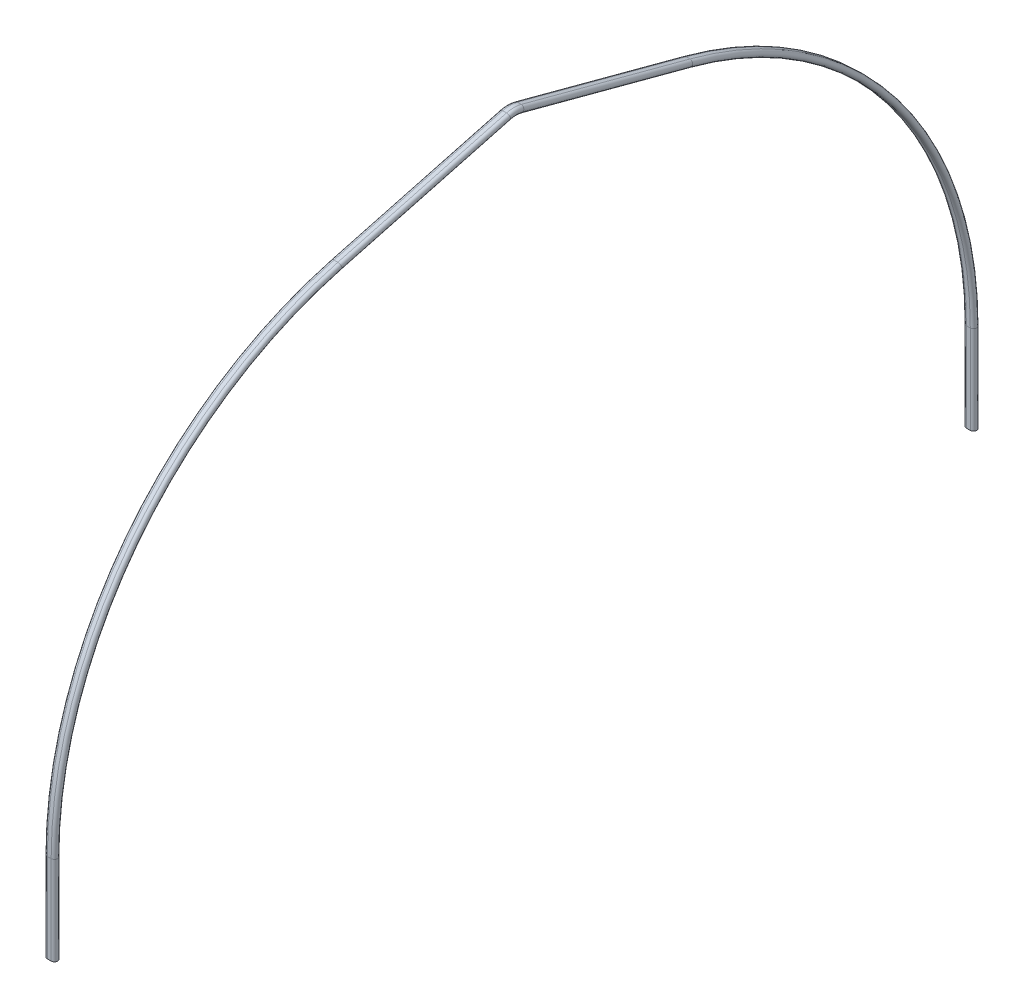
SolidWorks part; units mm, degrees
ref_plane "Front Plane" through (0, 0, 0) normal (0, 0, 1) x (1, 0, 0)
ref_plane "Top Plane" through (0, 0, 0) normal (0, 1, 0) x (1, 0, 0)
ref_plane "Right Plane" through (0, 0, 0) normal (1, 0, 0) x (0, 0, -1)
sketch "Sketch1" plane through (0, 0, 0) normal (0, 1, 0) x (1, 0, 0)
  line L0 (0, 0) -> (38.1, 0) construction
  line L1 (0, 31.75) -> (38.1, 31.75)
  line L2 (0, -31.75) -> (38.1, -31.75)
  line L3 (0, 0) -> (38.1, 0) construction
  line L4 (0, 20.3048) -> (38.1, 20.3048)
  line L5 (0, -20.3048) -> (38.1, -20.3048)
  arc A0 (0, 31.75) -> (0, -31.75) centre (0, 0) ccw
  arc A1 (38.1, -31.75) -> (38.1, 31.75) centre (38.1, 0) ccw
  arc A2 (0, 20.3048) -> (0, -20.3048) centre (0, 0) ccw
  arc A3 (38.1, -20.3048) -> (38.1, 20.3048) centre (38.1, 0) ccw
  point P3 (19.05, 0)
  point P10 (19.05, 0)
  dimension "D1" = 38.1
  dimension "D2" = 63.5
sketch "Sketch4" plane through (0, 0, 0) normal (1, 0, 0) x (0, 0, -1)
  line L0 (0, 0) -> (0, 882.8596)
  line L1 (6315.6947, 4564.2147) -> (4637.4463, 5011.7476)
  line L2 (0, 0) -> (4572, 0) construction
  line L3 (4572, 0) -> (4572, 5029.2) construction
  line L4 (2828.3053, 4564.2147) -> (4506.5537, 5011.7476)
  line L5 (9144, 0) -> (9144, 882.8596)
  line L6 (0, 3810) -> (7772.8418, 3810) construction
  arc A0 (0, 882.8596) -> (2828.3053, 4564.2147) centre (3810, 882.8596) cw
  arc A1 (9144, 882.8596) -> (6315.6947, 4564.2147) centre (5334, 882.8596) ccw
  arc A2 (4506.5537, 5011.7476) -> (4637.4463, 5011.7476) centre (4572, 4766.324) cw
  point P8 (0, 3810)
  dimension "D2" = 4572
  dimension "D4" = 3810
  dimension "D5" = 254
  dimension "D1" = 3810
  dimension "D3" = 5029.2
sweep "Sweep1" add profiles "Sketch1" path "Sketch4"
sketch "Sketch8" plane through (0, 0, 0) normal (1, 0, 0) x (0, 0, -1)
  line L0 (4572, 5052.074) -> (4572, 4988.574) construction
  line L1 (4572, 5020.324) -> (4639.7333, 5020.324) construction
  line L2 (4645.6271, 5042.4256) -> (4629.2655, 4981.0697) construction
  line L3 (4572, 5020.324) -> (4504.2667, 5020.324) construction
  line L4 (4498.3729, 5042.4256) -> (4514.7345, 4981.0697) construction
  arc A0 (4645.6271, 5042.4256) -> (4498.3729, 5042.4256) centre (4572, 4766.324) ccw construction
  arc A1 (4629.2655, 4981.0697) -> (4514.7345, 4981.0697) centre (4572, 4766.324) ccw construction
